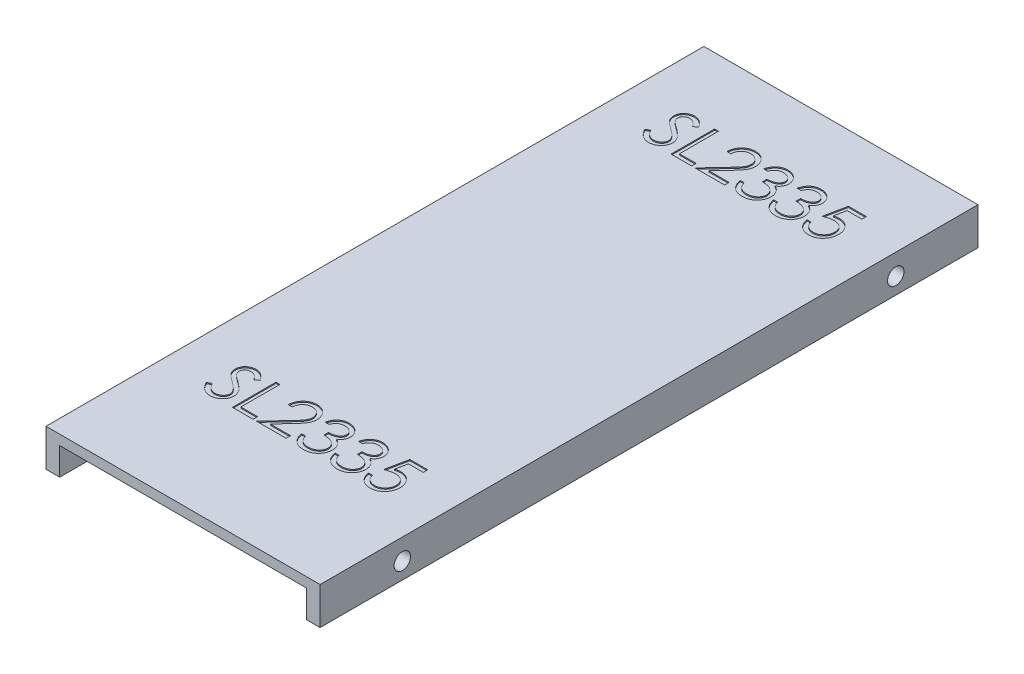
SolidWorks part; units mm, degrees
ref_plane "Front Plane" through (0, 0, 0) normal (0, 0, 1) x (1, 0, 0)
ref_plane "Top Plane" through (0, 0, 0) normal (0, 1, 0) x (1, 0, 0)
ref_plane "Right Plane" through (0, 0, 0) normal (1, 0, 0) x (0, 0, -1)
sketch "Sketch1" plane through (0, 0, 0) normal (0, 0, 1) x (1, 0, 0)
  line L1 (0, 0) -> (25, 0)
  line L2 (0, 0) -> (0, 68)
  line L4 (25, 0) -> (25, 50)
  line L5 (0, 68) -> (500, 68)
  line L7 (25, 50) -> (475, 50)
  line L10 (500, 68) -> (500, 0)
  line L11 (500, 0) -> (475, 0)
  line L12 (475, 50) -> (475, 0)
  dimension "D1" = 25
  dimension "D2" = 68
  dimension "D3" = 50
  dimension "D5" = 25
  dimension "D6" = 68
extrude "Boss-Extrude1" add sketch "Sketch1" along normal blind 1200
sketch "Sketch2" plane through (500, 0, 0) normal (1, 0, 0) x (0, 0, -1)
  line L0 (-1200, 0) -> (0, 0) construction
  line L1 (-1200, 0) -> (-1200, 68) construction
  circle A0 centre (-1050, 30) radius 15
  dimension "D1" = 30
  dimension "D2" = 30
  dimension "D3" = 150
extrude "Cut-Extrude1" cut sketch "Sketch2" against normal blind 1200
sketch "Sketch4" plane through (500, 0, 0) normal (1, 0, 0) x (0, 0, -1)
  line L0 (-1200, 0) -> (0, 0) construction
  line L1 (0, 0) -> (0, 68) construction
  circle A0 centre (-150, 30) radius 15
  dimension "D1" = 30
  dimension "D2" = 30
  dimension "D3" = 150
extrude "Cut-Extrude2" cut sketch "Sketch4" against normal blind 1200
sketch "Sketch9" plane through (0, 68, 0) normal (0, 1, 0) x (1, 0, 0)
  line L2 (0, -1200) -> (0, 0) construction
  line L3 (500, 0) -> (0, 0) construction
  text T0 "SL2335" font "Century Gothic" height in points 300
  point P6 (0, 0)
  point P7 (0, 0)
  point P8 (0, 0)
  dimension "D1" = 75
  dimension "D2" = 200
extrude "Cut-Extrude3" cut sketch "Sketch9" against normal blind 2
sketch "Sketch11" plane through (0, 68, 0) normal (0, 1, 0) x (1, 0, 0)
  line L0 (0, -1200) -> (0, 0) construction
  line L1 (500, -1200) -> (0, -1200) construction
  text T0 "SL2335" font "Century Gothic" height in points 300
  dimension "D1" = 75
  dimension "D2" = 200
extrude "Cut-Extrude6" cut sketch "Sketch11" against normal blind 2
